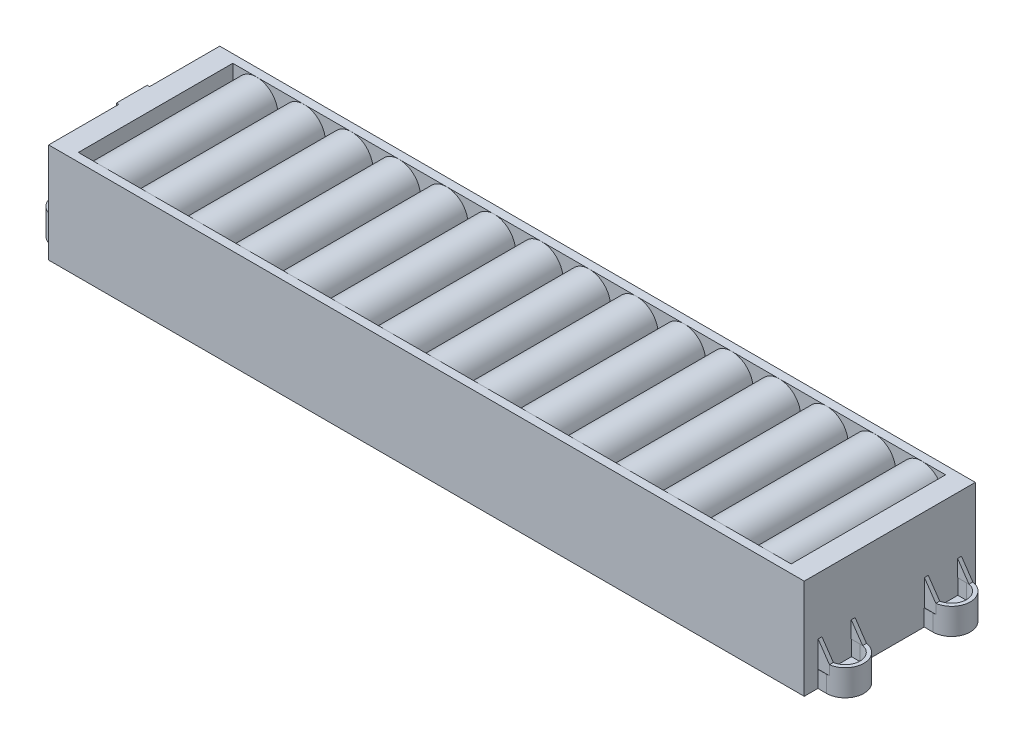
SolidWorks part; units mm, degrees
ref_plane "Front Plane" through (0, 0, 0) normal (0, 0, 1) x (1, 0, 0)
ref_plane "Top Plane" through (0, 0, 0) normal (0, 1, 0) x (1, 0, 0)
ref_plane "Right Plane" through (0, 0, 0) normal (1, 0, 0) x (0, 0, -1)
sketch "Sketch1" plane through (0, 0, 0) normal (0, 1, 0) x (1, 0, 0)
  line L1 (159, -36) -> (-159, -36)
  line L2 (159, -36) -> (159, 36)
  line L3 (159, 36) -> (-159, 36)
  line L4 (-159, -36) -> (-159, 36)
  line L5 (159, -36) -> (-159, 36) construction
  line L6 (159, 36) -> (-159, -36) construction
  point P0 (0, 0)
  dimension "D1" = 318
  dimension "D2" = 72
extrude "Boss-Extrude1" add sketch "Sketch1" along normal blind 42
sketch "Sketch2" plane through (0, 0, 0) normal (0, -1, 0) x (1, 0, 0)
  line L0 (162.625, 14.5) -> (159, 14.5)
  line L1 (159, 36) -> (159, -36) construction
  line L2 (162.625, 30.25) -> (159, 30.25)
  line L4 (162.625, 16.1) -> (159, 16.1)
  line L5 (162.625, 28.65) -> (159, 28.65)
  line L7 (159, 30.25) -> (159, 28.65)
  line L8 (159, 16.1) -> (159, 14.5)
  line L9 (162.625, -14.5) -> (159, -14.5)
  line L10 (159, -14.5) -> (159, -16.1)
  line L11 (159, -30.25) -> (162.625, -30.25)
  line L12 (159, -28.65) -> (162.625, -28.65)
  line L13 (162.625, -16.1) -> (159, -16.1)
  line L14 (159, -28.65) -> (159, -30.25)
  line L15 (-162.625, -14.5) -> (-159, -14.5)
  line L16 (-159, -36) -> (-159, 36) construction
  line L17 (-159, -14.5) -> (-159, -16.1)
  line L18 (-159, -30.25) -> (-162.625, -30.25)
  line L19 (-162.625, 14.5) -> (-159, 14.5)
  line L20 (-159, 14.5) -> (-159, 16.1)
  line L21 (-159, 30.25) -> (-162.625, 30.25)
  line L22 (-159, 28.65) -> (-162.625, 28.65)
  line L23 (-162.625, 16.1) -> (-159, 16.1)
  line L24 (-159, -28.65) -> (-162.625, -28.65)
  line L25 (-162.625, -16.1) -> (-159, -16.1)
  line L26 (-159, -28.65) -> (-159, -30.25)
  line L27 (-159, 28.65) -> (-159, 30.25)
  arc A0 (162.625, 14.5) -> (162.625, 30.25) centre (162.625, 22.375) ccw
  arc A1 (162.625, 16.1) -> (162.625, 28.65) centre (162.625, 22.375) ccw
  arc A2 (162.625, -30.25) -> (162.625, -14.5) centre (162.625, -22.375) ccw
  arc A3 (162.625, -28.65) -> (162.625, -16.1) centre (162.625, -22.375) ccw
  arc A4 (-162.625, 30.25) -> (-162.625, 14.5) centre (-162.625, 22.375) ccw
  arc A5 (-162.625, -14.5) -> (-162.625, -30.25) centre (-162.625, -22.375) ccw
  arc A6 (-162.625, 28.65) -> (-162.625, 16.1) centre (-162.625, 22.375) ccw
  arc A7 (-162.625, -16.1) -> (-162.625, -28.65) centre (-162.625, -22.375) ccw
  point P8 (159, 0)
  point P9 (170.5, 22.375)
  point P15 (170.5, -22.375)
  point P26 (-170.5, 22.375)
  point P28 (-170.5, -22.375)
  point P40 (-159, 0)
  dimension "D1" = 14.5
  dimension "D2" = 15.75
  dimension "D3" = 11.5
  dimension "D5" = 14.5
  dimension "D6" = 15.75
  dimension "D7" = 11.5
  dimension "D9" = 14.5
  dimension "D10" = 14.5
  dimension "D11" = 15.75
  dimension "D12" = 15.75
  dimension "D13" = 11.5
  dimension "D14" = 11.5
  dimension "D4" = 1.6
  dimension "D8" = 1.6
  dimension "D15" = 1.6
  dimension "D16" = 1.6
extrude "Boss-Extrude2" add sketch "Sketch2" against normal blind 11 separate body
sketch "Sketch3" plane through (0, 0, 0) normal (0, -1, 0) x (1, 0, 0)
  line L0 (159, 28.65) -> (159, 16.1)
  line L1 (159, 16.1) -> (162.625, 16.1)
  line L2 (162.625, 28.65) -> (159, 28.65)
  line L3 (161.825, 22.375) -> (165.075, 22.375) construction
  line L4 (161.825, 24.55) -> (165.075, 24.55)
  line L5 (161.825, 20.2) -> (165.075, 20.2)
  arc A0 (162.625, 28.65) -> (162.625, 16.1) centre (162.625, 22.375) cw
  arc A1 (161.825, 24.55) -> (161.825, 20.2) centre (161.825, 22.375) ccw
  arc A2 (165.075, 20.2) -> (165.075, 24.55) centre (165.075, 22.375) ccw
  arc A3 (162.625, 14.5) -> (162.625, 30.25) centre (162.625, 22.375) ccw construction
  point P13 (163.45, 22.375)
  point P18 (167.25, 22.375)
  point P19 (170.5, 22.375)
  dimension "D1" = 2.175
  dimension "D2" = 3.25
  dimension "D3" = 3.25
extrude "Boss-Extrude3" add sketch "Sketch3" against normal blind 4.5
mirror "Mirror5" about plane through (0, 0, 0) normal (1, 0, 0) of "Boss-Extrude3" second plane through (0, 0, 0) second plane normal (0, 0, 1)
sketch "Sketch4" plane through (0, 0, 0) normal (0, 0, 1) x (1, 0, 0)
  line L2 (-159, 42) -> (159, 42) construction
  line L3 (-159, 42) -> (-159, 0) construction
  line L10 (-131, 33) -> (-130, 33)
  line L11 (-130, 33) -> (-130, 42)
  line L12 (-159, 42) -> (159, 42) construction
  line L13 (-130, 42) -> (-150, 42)
  line L14 (-150, 42) -> (-150, 33)
  line L15 (-150, 33) -> (-149, 33)
  arc A0 (-131, 33) -> (-149, 33) centre (-140, 33) ccw
  point P2 (-140, 42)
  dimension "D1" = 18
  dimension "D2" = 19
  dimension "D3" = 1
  dimension "D4" = 1
extrude "Cut-Extrude1" cut sketch "Sketch4" against normal blind 32.5 and the other way blind 32.5 contours A0 L15 | A0 region at (-132.154, 39.1404, 0) region at (-147.846, 39.1404, 0)
pattern_linear "LPattern1" count 15 spacing 20 along (1, 0, 0) of "Cut-Extrude1"
ref_plane "Plane1" through (0, 21, 0) normal (0, -1, 0) x (-1, 0, 0)
mirror "Mirror7" about plane through (0, 21, 0) normal (0, -1, 0) of "LPattern1"
sketch "Sketch5" plane through (0, 0, 36) normal (0, 0, 1) x (1, 0, 0)
  line L0 (159, 11) -> (163.8, 11)
  line L1 (170.5, 11) -> (162.625, 11) construction
  line L2 (163.8, 11) -> (159, 18)
  line L3 (159, 42) -> (159, 0) construction
  line L4 (159, 18) -> (159, 11)
  dimension "D1" = 7
  dimension "D2" = 4.8
extrude "Boss-Extrude4" add sketch "Sketch5" against normal through all
sketch "Sketch6" plane through (0, 42, 0) normal (0, 1, 0) x (1, 0, 0)
  line L0 (159, -36) -> (159, 36) construction
  line L1 (159, -36) -> (163.8, -36)
  line L2 (159, -36) -> (159, -30.1618)
  line L3 (159, -30.1618) -> (163.8, -30.1618)
  line L4 (163.8, -36) -> (163.8, -30.1618)
  line L5 (163.8, -28.539) -> (159, -28.539)
  line L6 (163.8, -28.539) -> (163.8, -16.211)
  line L7 (163.8, -16.211) -> (159, -16.211)
  line L8 (159, -28.539) -> (159, -16.211)
  line L9 (163.8, -16.211) -> (163.8, -28.539) construction
  line L10 (159, 36) -> (159, -36) construction
  line L11 (163.8, -14.5882) -> (159, -14.5882)
  line L12 (163.8, -14.5882) -> (163.8, 14.5882)
  line L13 (163.8, 14.5882) -> (159, 14.5882)
  line L14 (159, -14.5882) -> (159, 14.5882)
  line L15 (163.8, 14.5882) -> (163.8, -14.5882) construction
  line L16 (163.8, 28.539) -> (163.8, 16.211) construction
  line L17 (163.8, 16.211) -> (159, 16.211)
  line L18 (163.8, 16.211) -> (163.8, 28.539)
  line L19 (163.8, 28.539) -> (159, 28.539)
  line L20 (159, 16.211) -> (159, 28.539)
  line L22 (159, 36) -> (163.8, 36)
  line L23 (159, 36) -> (159, 30.1618)
  line L24 (159, 30.1618) -> (163.8, 30.1618)
  line L25 (163.8, 36) -> (163.8, 30.1618)
  arc A0 (162.625, -28.65) -> (162.625, -16.1) centre (162.625, -22.375) ccw construction
  arc A1 (163.8, 14.5882) -> (163.8, 30.1618) centre (162.625, 22.375) ccw construction
  arc A2 (162.625, 16.1) -> (162.625, 28.65) centre (162.625, 22.375) ccw construction
extrude "Cut-Extrude2" cut sketch "Sketch6" against normal blind 35
sketch "Sketch7" plane through (-159, 0, 0) normal (-1, 0, 0) x (0, 0, 1)
  line L0 (-36, 42) -> (36, 42) construction
  line L1 (-6.5, 42) -> (6.5, 42)
  line L2 (-6.5, 42) -> (-6.5, 32)
  line L3 (-6.5, 32) -> (6.5, 32)
  line L4 (6.5, 42) -> (6.5, 32)
  point P6 (0, 42)
  point P7 (0, 42)
  dimension "D1" = 13
  dimension "D2" = 10
extrude "Boss-Extrude5" add sketch "Sketch7" along normal blind 1
sketch "Sketch8" plane through (0, 4.5, 0) normal (0, 1, 0) x (1, 0, 0)
  line L1 (-168.9, -22.375) -> (-159, -22.375) construction
  line L2 (-159, -28.65) -> (-159, -16.1) construction
  line L3 (-159, -6.5) -> (-159, -36) construction
  line L4 (-162.625, -28.65) -> (-159, -28.65) construction
  line L5 (-159, -16.1) -> (-162.625, -16.1) construction
  line L6 (-162.625, -28.65) -> (-159, -28.65)
  line L7 (-159, -16.1) -> (-162.625, -16.1)
  line L8 (-159, -28.65) -> (-159, -16.1)
  arc A1 (-162.625, -16.1) -> (-162.625, -28.65) centre (-162.625, -22.375) ccw construction
  circle A2 centre (-164, -22.375) radius 4.75
  arc A3 (-162.625, -16.1) -> (-162.625, -28.65) centre (-162.625, -22.375) ccw
  dimension "D1" = 5
  dimension "D2" = 9.5
extrude "Boss-Extrude6" add sketch "Sketch8" along normal up to surface (6.5 mm away) up to face at (-162.5813, 11, 22.375)
mirror "Mirror8" about plane through (0, 0, 0) normal (0, 0, 1) of "Boss-Extrude6"
sketch "Sketch9" plane through (0, 4.5, 0) normal (0, 1, 0) x (1, 0, 0)
  line L0 (-159.65, 22.375) -> (-167.25, 22.375) construction
  line L1 (167.25, 22.375) -> (159.65, 22.375) construction
  line L2 (167.25, -22.375) -> (159, -22.375)
  line L3 (159, -28.65) -> (159, -16.1) construction
  arc A0 (-161.825, 20.2) -> (-161.825, 24.55) centre (-161.825, 22.375) ccw construction
  arc A1 (-165.075, 24.55) -> (-165.075, 20.2) centre (-165.075, 22.375) ccw construction
  arc A2 (165.075, 20.2) -> (165.075, 24.55) centre (165.075, 22.375) ccw construction
  arc A3 (161.825, 24.55) -> (161.825, 20.2) centre (161.825, 22.375) ccw construction
  arc A4 (165.075, -24.55) -> (165.075, -20.2) centre (165.075, -22.375) ccw construction
  point P16 (-163.45, 22.375)
  point P17 (163.45, 22.375)
  dimension "D1" = 326.9
  dimension "D2" = 44.75
equation "\"D1@Sketch2\"=29/2"
equation "\"D1@Sketch3\"=4.35/2"
equation "\"D2@Sketch3\"=7.6-2*\"D1@Sketch3\""
equation "\"D5@Sketch2\"=\"D1@Sketch2\""
equation "\"D6@Sketch2\"=\"D2@Sketch2\""
equation "\"D7@Sketch2\"=\"D3@Sketch2\""
equation "\"D9@Sketch2\"=\"D1@Sketch2\""
equation "\"D10@Sketch2\"=\"D1@Sketch2\""
equation "\"D11@Sketch2\"=\"D2@Sketch2\""
equation "\"D12@Sketch2\"=\"D2@Sketch2\""
equation "\"D13@Sketch2\"=\"D3@Sketch2\""
equation "\"D14@Sketch2\"=\"D3@Sketch2\""
